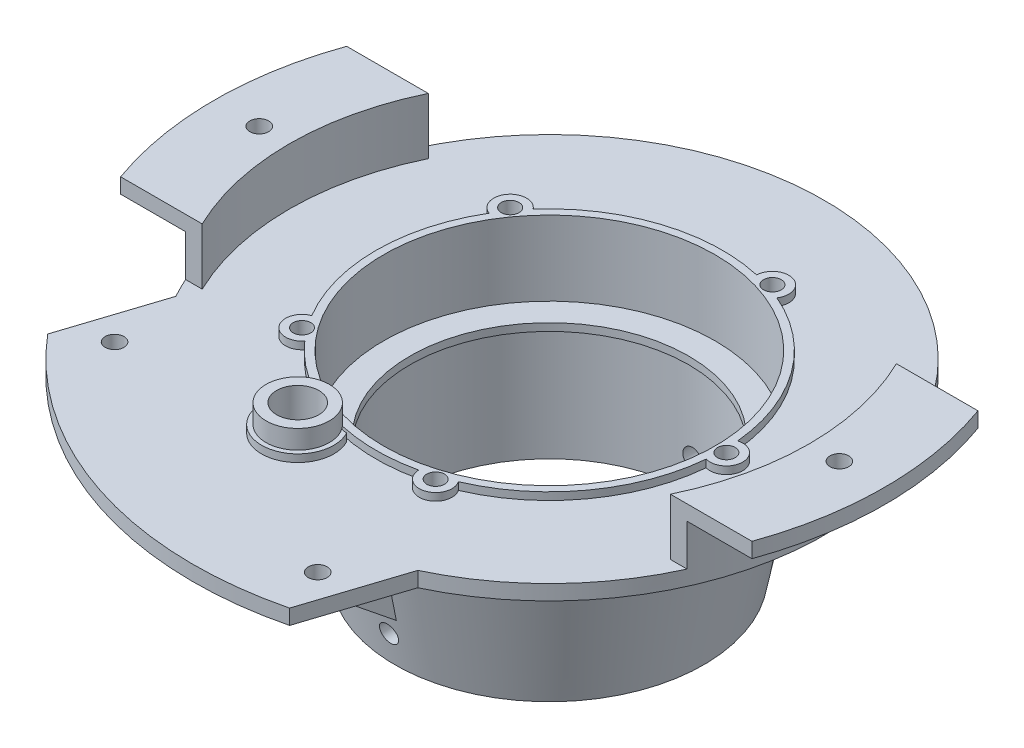
SolidWorks part; units mm, degrees
ref_plane "Front Plane" through (0, 0, 0) normal (0, 0, 1) x (1, 0, 0)
ref_plane "Top Plane" through (0, 0, 0) normal (0, 1, 0) x (1, 0, 0)
ref_plane "Right Plane" through (0, 0, 0) normal (1, 0, 0) x (0, 0, -1)
sketch "Sketch1" plane through (0, 0, 0) normal (0, 0, 1) x (1, 0, 0)
  line L26 (-73, -4) -> (-73, 11)
  line L27 (-73, 11) -> (-89, 11)
  line L28 (-89, 11) -> (-89, 15)
  line L29 (-89, 15) -> (-69, 15)
  line L30 (-69, 15) -> (-69, 0)
  line L31 (-69, 0) -> (-44, 0)
  line L36 (-38, -19.8) -> (-38, -49.8)
  line L37 (-38, -49.8) -> (-41, -49.8)
  line L38 (-40, -17.8) -> (-37, -17.8)
  line L41 (-40, -17.8) -> (-44, -17.8)
  line L42 (-44, 0) -> (-44, -17.8)
  line L43 (-37, -17.8) -> (-37, -19.8)
  line L44 (-37, -19.8) -> (-38, -19.8)
  line L45 (-73, -4) -> (-59, -4)
  line L47 (-48, -15) -> (-41, -49.8)
  line L48 (-59, -4) -> (-48, -15)
  dimension "D2" = 4
  dimension "D3" = 37
  dimension "D4" = 44
  dimension "D5" = 17.8
  dimension "D6" = 2
  dimension "D7" = 15
  dimension "D8" = 4
  dimension "D9" = 38
  dimension "D10" = 3
  dimension "D11" = 20
  dimension "D12" = 4
  dimension "D13" = 4
  dimension "D14" = 30
  dimension "D15" = 4
  dimension "D16" = 25
  dimension "D17" = 15
  dimension "D18" = 15
ref_axis "Axis1" through (0, -100.5, 0) along (0, 1, 0)
revolve "Revolve1" add sketch "Sketch1" angle 360 about axis through (0, -100.5, 0) along (0, 1, 0)
sketch "Sketch2" plane through (0, 11, 0) normal (0, -1, 0) x (1, 0, 0)
  circle A0 centre (77, 0) radius 2.5
  circle A1 centre (-77, 0) radius 2.5
  dimension "D1" = 5
  dimension "D3" = 77
  dimension "D2" = 77
extrude "Cut-Extrude3" cut sketch "Sketch2" against normal up to surface (4 mm away) up to face at (0, 15, -89)
sketch "Sketch3" plane through (0, 15, 0) normal (0, 1, 0) x (1, 0, 0)
  line L0 (-62.1369, -30) -> (-83.7914, -30)
  line L1 (83.7914, -30) -> (62.1369, -30)
  line L5 (83.7914, 30) -> (62.1369, 30)
  line L9 (-62.1369, 30) -> (-83.7914, 30)
  circle A0 centre (0, 0) radius 89 construction
  circle A1 centre (-77, 0) radius 2.5 construction
  arc A2 (-83.7914, -30) -> (83.7914, -30) centre (0, 0) ccw
  circle A3 centre (0, 0) radius 69 construction
  arc A4 (-62.1369, -30) -> (62.1369, -30) centre (0, 0) ccw
  arc A5 (62.1369, 30) -> (-62.1369, 30) centre (0, 0) ccw
  arc A6 (83.7914, 30) -> (-83.7914, 30) centre (0, 0) ccw
  dimension "D2" = 30
  dimension "D1" = 30
extrude "Cut-Extrude4" cut sketch "Sketch3" against normal up to surface (15 mm away) up to face at (0, 0, -69)
sketch "Sketch6" plane through (0, 0, 0) normal (0, 0, 1) x (1, 0, 0)
  line L0 (0, -100.5) -> (0, 20.5) construction
  line L2 (-41, -49.8) -> (41, -49.8) construction
  circle A0 centre (0, -41.8) radius 2.5
  dimension "D1" = 5
  dimension "D2" = 8
extrude "Cut-Extrude6" cut sketch "Sketch6" against normal through all both and the other way through all
sketch "Sketch7" plane through (0, 0, 0) normal (0, 1, 0) x (1, 0, 0)
  circle A0 centre (47, 0) radius 2.35
  dimension "D1" = 4.7
  dimension "D2" = 47
extrude "Cut-Extrude7" cut sketch "Sketch7" against normal up to surface (15.9413 mm away) contours A0 up to face at (0, -15, -48)
pattern_circular "CirPattern1" count 5 every 72 about axis through (0, -100.5, 0) along (0, 1, 0) of "Cut-Extrude7"
sketch "Sketch9" plane through (0, 0, 0) normal (0, 1, 0) x (1, 0, 0)
  circle A0 centre (-16.377, -50.4063) radius 5.6
  circle A3 centre (-38.0238, -27.6259) radius 2.35 construction
  circle A4 centre (14.5238, -44.6997) radius 2.35 construction
  dimension "D1" = 11.2
  dimension "D3" = 31.425
  dimension "D2" = 53
  dimension "D4" = 31.4233
extrude "Cut-Extrude8" cut sketch "Sketch9" against normal through all contours A0
sketch "Sketch8" plane through (0, 0, 0) normal (0, 1, 0) x (1, 0, 0)
  circle A0 centre (0, 0) radius 44 construction
  circle A1 centre (0, 0) radius 44
  arc A2 (-34.6013, -30.3109) -> (-18.305, -42.201) centre (0, 0) ccw
  circle A3 centre (-38.0238, -27.6259) radius 2.35 construction
  circle A4 centre (14.5238, -44.6997) radius 2.35 construction
  circle A5 centre (47, 0) radius 2.35 construction
  circle A6 centre (14.5238, 44.6997) radius 2.35 construction
  circle A7 centre (-38.0238, 27.6259) radius 2.35 construction
  circle A8 centre (-38.0238, -27.6259) radius 2.35
  circle A9 centre (14.5238, -44.6997) radius 2.35
  circle A10 centre (47, 0) radius 2.35
  circle A11 centre (14.5238, 44.6997) radius 2.35
  circle A12 centre (-38.0238, 27.6259) radius 2.35
  arc A13 (-34.6013, 30.3109) -> (-39.5198, 23.5412) centre (-38.0238, 27.6259) ccw
  arc A14 (18.135, 42.2744) -> (10.1768, 44.8602) centre (14.5238, 44.6997) ccw
  arc A15 (45.8093, -4.1839) -> (45.8093, 4.1839) centre (47, 0) ccw
  arc A16 (10.1768, -44.8602) -> (18.135, -42.2744) centre (14.5238, -44.6997) ccw
  arc A17 (-39.5198, -23.5412) -> (-34.6013, -30.3109) centre (-38.0238, -27.6259) ccw
  arc A18 (18.135, -42.2744) -> (45.8093, -4.1839) centre (0, 0) ccw
  circle A19 centre (-38.0238, -27.6259) radius 4.35 construction
  circle A20 centre (0, 0) radius 46 construction
  circle A21 centre (14.5238, -44.6997) radius 4.35 construction
  arc A22 (45.8093, 4.1839) -> (18.135, 42.2744) centre (0, 0) ccw
  arc A23 (10.1768, 44.8602) -> (-34.6013, 30.3109) centre (0, 0) ccw
  circle A24 centre (47, 0) radius 4.35 construction
  arc A25 (-39.5198, 23.5412) -> (-39.5198, -23.5412) centre (0, 0) ccw
  circle A26 centre (14.5238, 44.6997) radius 4.35 construction
  circle A27 centre (-38.0238, 27.6259) radius 4.35 construction
  circle A28 centre (-16.377, -50.4063) radius 5.6 construction
  circle A29 centre (-16.377, -50.4063) radius 5.6
  arc A30 (-21.1319, -42.0666) -> (-7.9084, -45.8849) centre (-16.377, -50.4063) ccw
  arc A31 (-18.305, -42.201) -> (-21.1319, -42.0666) centre (-19.5582, -38.7645) cw
  arc A32 (-10.7379, -44.7292) -> (-7.9084, -45.8849) centre (-8.0531, -42.1977) ccw
  arc A33 (-10.7379, -44.7292) -> (10.1768, -44.8602) centre (0, 0) ccw
  circle A34 centre (-16.377, -50.4063) radius 9.6 construction
  point P4 (18.6238, -44.6997)
  point P23 (-33.9238, 27.6259)
  point P29 (41.5993, 12.7182)
  point P30 (-33.9238, -27.6259)
  point P39 (51.1, 0)
  point P42 (18.6238, 44.6997)
  point P57 (-8.777, -50.4063)
  dimension "D1" = 2
  dimension "D2" = 2
  dimension "D3" = 4
extrude "Boss-Extrude1" add sketch "Sketch8" along normal blind 2
sketch "Sketch10" plane through (0, 2, 0) normal (0, 1, 0) x (1, 0, 0)
  circle A0 centre (-16.377, -50.4063) radius 5.6 construction
  circle A1 centre (-16.377, -50.4063) radius 5.6
  circle A2 centre (-16.377, -50.4063) radius 8.4
  dimension "D1" = 2.8
extrude "Boss-Extrude2" add sketch "Sketch10" along normal blind 5
ref_point "Point1"
sketch "Sketch15" plane through (0, 0, 0) normal (0, 1, 0) x (1, 0, 0)
  line L0 (0, 0) -> (-16.377, -50.4063)
  line L1 (-16.377, -50.4063) -> (-33.367, -102.6994)
sketch "Sketch11" plane through (0, 0, 0) normal (0, 1, 0) x (1, 0, 0)
  line L0 (-63.9883, -35.1354) -> (-72.3314, -60.8146)
  line L1 (31.1179, -66.0354) -> (22.7748, -91.7146)
  line L3 (-16.377, -50.4063) -> (-33.367, -102.6994) construction
  arc A0 (-66.5507, -30) -> (66.5507, -30) centre (0, 0) ccw construction
  arc A1 (-63.9883, -35.1354) -> (31.1179, -66.0354) centre (0, 0) ccw
  arc A4 (22.7748, -91.7146) -> (-72.3314, -60.8146) centre (0, 0) cw
  point P3 (0, 0)
  point P4 (-86.4221, -40.6383)
  point P5 (86.4221, -40.6383)
  point P11 (-22.557, -69.4275)
  point P14 (-29.2005, -89.8754)
  dimension "D2" = 21.5
  dimension "D1" = 100
extrude "Boss-Extrude3" add sketch "Sketch11" against normal up to surface (4 mm away) up to face at (0, -4, -59)
ref_axis "Axis2" through (22.7748, 0, 91.7146) along (-0.9511, 0, -0.309)
sketch "Sketch16" plane through (0, 0, 0) normal (0, 1, 0) x (1, 0, 0)
  line L0 (22.7748, -91.7146) -> (31.1179, -66.0354) construction
  line L1 (-63.9883, -35.1354) -> (-72.3314, -60.8146) construction
  line L2 (22.7748, -91.7146) -> (-72.3314, -60.8146) construction
  circle A0 centre (18.2563, -79.7319) radius 2.5
  circle A1 centre (-61.6329, -53.776) radius 2.5
  dimension "D3" = 5
  dimension "D4" = 10
  dimension "D5" = 10
  dimension "D1" = 8
  dimension "D2" = 8
extrude "Cut-Extrude9" cut sketch "Sketch16" against normal up to surface (4 mm away) up to face at (0, -4, -59)
sketch "Sketch17" plane through (0, 0, 0) normal (0, 1, 0) x (1, 0, 0)
  line L0 (0, 0) -> (-56.2218, -75.9563)
  line L1 (0, 0) -> (0.8419, -94.4962)
  line L2 (-56.2218, -75.9563) -> (0.8419, -94.4962)
  line L3 (0, 0) -> (-16.377, -50.4063)
  line L4 (-16.377, -50.4063) -> (-33.0404, -101.6941)
  arc A0 (-72.3314, -60.8146) -> (22.7748, -91.7146) centre (0, 0) ccw construction
  point P10 (-27.69, -85.2263)
  dimension "D1" = 60
ref_plane "Plane2" through (0, 0, 0) normal (-0.8038, 0, -0.5949) x (-0.5949, 0, 0.8038)
ref_plane "Plane3" through (0, 0, 0) normal (-1, 0, 0.0089) x (0.0089, 0, 1)
sketch "Sketch18" plane through (0, 0, 0) normal (-0.8038, 0, -0.5949) x (-0.5949, 0, 0.8038)
  line L2 (91.9138, -4) -> (66.31, -4) construction
  line L27 (29.5895, -15) -> (44.6985, -15) construction
  line L29 (44.8194, -15) -> (42.0003, -38.1306)
  line L30 (42.0003, -38.1306) -> (84.2847, -4)
  line L31 (44.8194, -15) -> (55.4437, -4)
  line L32 (-59, -4) -> (59, -4) construction
  line L33 (55.4437, -4) -> (84.2847, -4)
extrude "Boss-Extrude8" add sketch "Sketch18" along normal mid plane 5
ref_plane "Plane4" through (0, 0, 0) normal (0.9511, 0, 0.309) x (0.309, 0, -0.9511)
mirror "Mirror1" about plane through (0, 0, 0) normal (0.9511, 0, 0.309) of "Boss-Extrude8"
